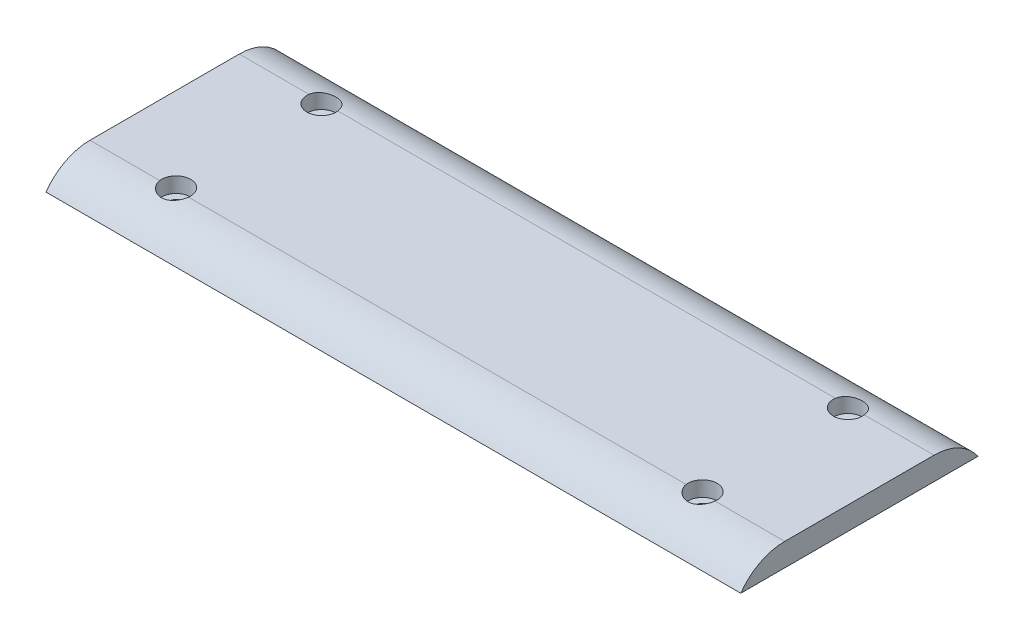
SolidWorks part; units mm, degrees
ref_plane "Front Plane" through (0, 0, 0) normal (0, 0, 1) x (1, 0, 0)
ref_plane "Top Plane" through (0, 0, 0) normal (0, 1, 0) x (1, 0, 0)
ref_plane "Right Plane" through (0, 0, 0) normal (1, 0, 0) x (0, 0, -1)
sketch "Sketch1" plane through (0, 0, 0) normal (0, 1, 0) x (1, 0, 0)
  line L0 (-45.4, 0) -> (45.4, 0) construction
  line L1 (-45.4, 15.5) -> (45.4, 15.5)
  line L2 (-45.4, 15.5) -> (-45.4, -15.5)
  line L3 (-45.4, -15.5) -> (45.4, -15.5)
  line L4 (45.4, 15.5) -> (45.4, -15.5)
  line L5 (0, 15.5) -> (0, -15.5) construction
  point P8 (0, 0)
  dimension "D1" = 90.8
  dimension "D2" = 31
extrude "Boss-Extrude1" add sketch "Sketch1" along normal blind 3
sketch "Sketch2" plane through (0, 3, 0) normal (0, 1, 0) x (1, 0, 0)
  line L0 (-34.4, 9.5) -> (-45.4, 9.5) construction
  line L1 (-45.4, 15.5) -> (-45.4, -15.5) construction
  line L2 (-34.4, -9.5) -> (-45.4, -9.5) construction
  line L3 (34.4, 9.5) -> (45.4, 9.5) construction
  line L4 (45.4, -15.5) -> (45.4, 15.5) construction
  line L5 (34.4, -9.5) -> (45.4, -9.5) construction
  line L6 (-34.4, 9.5) -> (-34.4, 15.5) construction
  line L7 (45.4, 15.5) -> (-45.4, 15.5) construction
  line L8 (34.4, 9.5) -> (34.4, 15.5) construction
  line L9 (34.4, -9.5) -> (34.4, -15.5) construction
  line L10 (-45.4, -15.5) -> (45.4, -15.5) construction
  line L11 (-34.4, -9.5) -> (-34.4, -15.5) construction
  circle A0 centre (-34.4, 9.5) radius 0.95
  circle A1 centre (34.4, 9.5) radius 0.95
  circle A2 centre (-34.4, -9.5) radius 0.95
  circle A3 centre (34.4, -9.5) radius 0.95
  dimension "D1" = 1.9
  dimension "D2" = 6
  dimension "D3" = 11
extrude "Cut-Extrude1" cut sketch "Sketch2" against normal blind 3
sketch "Sketch3" plane through (0, 3, 0) normal (0, 1, 0) x (1, 0, 0)
  circle A0 centre (-34.4, 9.5) radius 1.9
  circle A1 centre (-34.4, -9.5) radius 1.9
  circle A2 centre (34.4, 9.5) radius 1.9
  circle A3 centre (34.4, -9.5) radius 1.9
  dimension "D1" = 3.8
extrude "Cut-Extrude2" cut sketch "Sketch3" against normal blind 2
sketch "Sketch4" plane through (0, 0, 0) normal (0, -1, 0) x (1, 0, 0)
  line L0 (-27, 0) -> (27, 0) construction
  line L1 (-27, 3.5) -> (27, 3.5)
  line L2 (-27, 3.5) -> (-27, -3.5)
  line L3 (-27, -3.5) -> (27, -3.5)
  line L4 (27, 3.5) -> (27, -3.5)
  line L5 (0, 3.5) -> (0, -3.5) construction
  point P8 (0, 0)
  dimension "D1" = 54
  dimension "D2" = 7
extrude "Boss-Extrude2" add sketch "Sketch4" along normal blind 6
sketch "Sketch5" plane through (27, 0, 0) normal (1, 0, 0) x (0, 0, -1)
  line L0 (0, -6) -> (0, -7.1307) construction
  line L1 (3.5, -6) -> (-3.5, -6) construction
  circle A0 centre (0, -7.1307) radius 3.9
  dimension "D1" = 7.8
  dimension "D2" = 1.1307
extrude "Cut-Extrude3" cut sketch "Sketch5" against normal blind 54
fillet "Fillet1" radius 7 2 edges at (0, 3, 15.5) (0, 3, -15.5)
